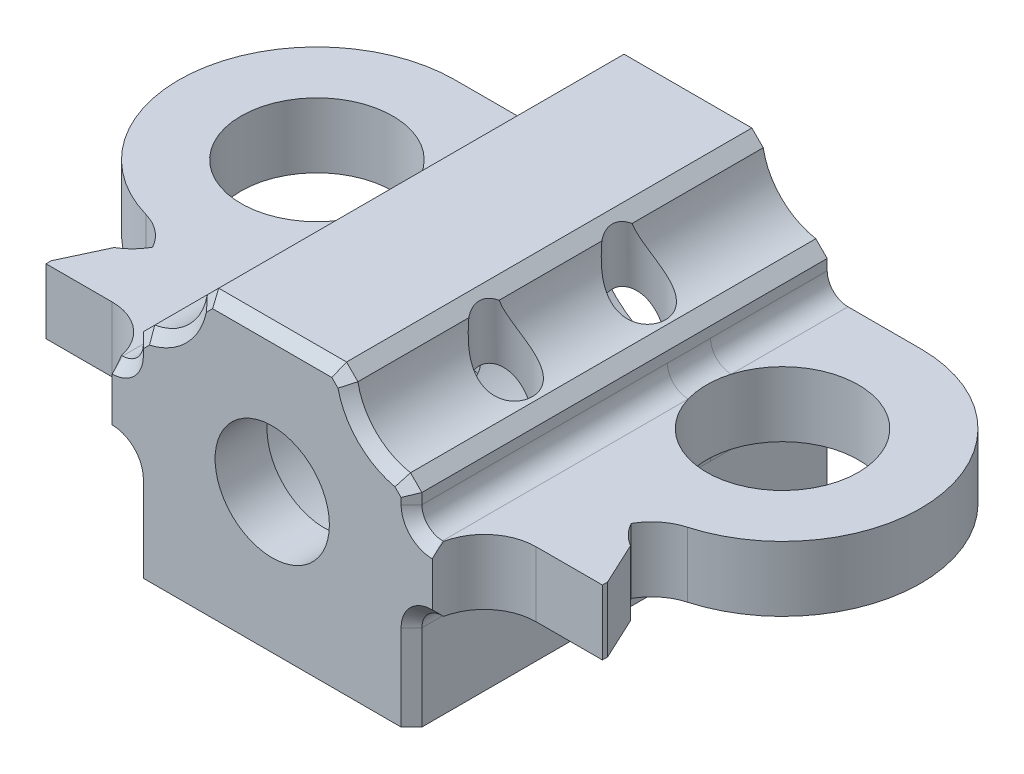
SolidWorks part; units mm, degrees
ref_plane "Front Plane" through (0, 0, 0) normal (0, 0, 1) x (1, 0, 0)
ref_plane "Top Plane" through (0, 0, 0) normal (0, 1, 0) x (1, 0, 0)
ref_plane "Right Plane" through (0, 0, 0) normal (1, 0, 0) x (0, 0, -1)
sketch "Sketch1" plane through (0, 0, 0) normal (0, 0, 1) x (1, 0, 0)
  line L0 (0, 0) -> (0, 69.4209) construction
  line L1 (8.509, 17.018) -> (-8.509, 17.018)
  line L2 (-8.509, 17.018) -> (-8.509, 0)
  line L3 (-8.509, 0) -> (8.509, 0)
  line L4 (8.509, 17.018) -> (8.509, 0)
  point P8 (0, 17.018)
  dimension "D1" = 17.018
  dimension "D2" = 17.018
extrude "Boss-Extrude1" add sketch "Sketch1" along normal blind 25.4
ref_plane "Plane1" through (0, 8.509, 0) normal (0, 1, 0) x (1, 0, 0)
sketch "Sketch2" plane through (0, 0, 0) normal (1, 0, 0) x (0, 0, -1)
  line L0 (-25.4, 8.509) -> (1.0345, 8.509) construction
  line L1 (-25.4, 0) -> (-25.4, 17.018) construction
  line L2 (-22.225, 14.859) -> (-15.3578, 14.859)
  line L3 (-22.225, 14.859) -> (-22.225, 12.0015)
  line L4 (-22.225, 12.0015) -> (-25.4, 12.0015)
  line L5 (-25.4, 12.0015) -> (-25.4, 8.509)
  line L6 (-15.3578, 14.859) -> (-15.3578, 3.977) construction
  line L7 (-25.4, 8.509) -> (-12.1828, 8.509)
  line L8 (-15.3578, 14.859) -> (0, 14.859)
  line L9 (0, 0) -> (0, 17.018) construction
  line L10 (-12.1828, 8.509) -> (0, 8.509)
  line L11 (0, 8.509) -> (0, 14.859)
  dimension "D1" = 12.7
  dimension "D2" = 6.985
  dimension "D3" = 3.175
revolve "Cut-Revolve1" cut sketch "Sketch2" angle 360 about L7
sketch "Sketch4" plane through (0, 0, 0) normal (0, -1, 0) x (1, 0, 0)
  line L1 (-6, 17.0663) -> (6, 17.0663) construction
  line L2 (-6, 17.0663) -> (-6, 9.0663) construction
  line L3 (-6, 9.0663) -> (6, 9.0663) construction
  line L4 (6, 17.0663) -> (6, 9.0663) construction
  line L5 (-6, 17.0663) -> (6, 9.0663) construction
  line L6 (-6, 9.0663) -> (6, 17.0663) construction
  line L15 (-8.509, 25.4) -> (8.509, 25.4) construction
  circle A0 centre (-6, 17.0663) radius 1.016
  circle A1 centre (5.938, 17.0663) radius 1.016
  circle A2 centre (5.938, 8.9383) radius 1.016
  circle A3 centre (-6, 8.9383) radius 1.016
  point P0 (0, 13.0663)
  dimension "D3" = 2.032
  dimension "D1" = 12
  dimension "D2" = 8
  dimension "D6" = 8.3337
  dimension "D4" = 2
  dimension "D5" = 2
extrude "Cut-Extrude2" cut sketch "Sketch4" against normal through all
sketch "Sketch5" plane through (0, 8.509, 0) normal (0, 1, 0) x (1, 0, 0)
  line L0 (8.509, 0) -> (14.224, 0)
  line L1 (16.9974, -21.9058) -> (15.776, -19.2866)
  line L2 (15.776, -19.2866) -> (14.224, -19.2866)
  line L3 (14.224, -19.2866) -> (14.224, -16.891)
  line L4 (8.509, -25.4) -> (16.9974, -25.4)
  line L5 (14.224, -8.4455) -> (21.1828, -23.3687) construction
  line L6 (16.9974, -21.9058) -> (16.9974, -25.4)
  line L7 (8.509, -25.4) -> (8.509, 0) construction
  line L8 (8.509, 0) -> (8.509, -25.4)
  line L10 (0, -25.4) -> (0, 11.748) construction
  line L11 (8.509, -25.4) -> (-8.509, -25.4) construction
  line L12 (14.224, -8.4455) -> (14.224, -36.5309) construction
  arc A0 (14.224, 0) -> (14.224, -16.891) centre (14.224, -8.4455) cw
  circle A1 centre (14.224, -8.4455) radius 4.6355
  dimension "D2" = 9.271
  dimension "D4" = 3.81
  dimension "D3" = 5.715
  dimension "D5" = 25
  dimension "D6" = 6.35
extrude "Boss-Extrude2" add sketch "Sketch5" against normal blind 1.9844 and the other way blind 1.9844
mirror "Mirror1" about plane through (0, 0, 0) normal (1, 0, 0) of "Boss-Extrude2"
fillet "Fillet2" radius 3.175 4 edges at (14.224, 8.509, 16.891) (14.224, 8.509, 19.2866) (-14.224, 8.509, 19.2866) (-14.224, 8.509, 16.891)
sketch "Sketch7" plane through (0, 0, 25.4) normal (0, 0, 1) x (1, 0, 0)
  line L0 (0, 19.0675) -> (0, -3.3693) construction
  circle A0 centre (8.509, 17.018) radius 3.9687
  circle A1 centre (-8.509, 17.018) radius 3.9687
  dimension "D1" = 7.9375
extrude "Cut-Extrude3" cut sketch "Sketch7" against normal through all
fillet "Fillet3" radius 1.27 4 edges
chamfer "Chamfer1" distance 0.635 angle 45 4 edges at (8.509, 13.0492, 12.7) (4.5402, 17.018, 12.7) (-4.5402, 17.018, 12.7) (-8.509, 13.0492, 12.7)
chamfer "Chamfer2" distance 0.635 angle 45 21 edges at (-8.881, 6.1527, 25.4) (-16.9974, 8.509, 25.4) (-8.881, 10.8653, 25.4) (-8.1607, 12.7626, 25.4) (-5.7027, 14.2117, 25.4) (-4.2536, 16.6697, 25.4) (8.881, 6.1527, 25.4) (16.9974, 8.509, 25.4) (8.881, 10.8653, 25.4) (8.1607, 12.7626, 25.4) (5.7027, 14.2117, 25.4) (4.2536, 16.6697, 25.4) (0, 17.018, 25.4)
sketch "Sketch8" plane through (0, 17.018, 0) normal (0, 1, 0) x (1, 0, 0)
  line L0 (-16.9974, -22.225) -> (-12.954, -22.225)
  line L1 (-16.9974, -24.765) -> (-16.9974, -21.9058) construction
  line L3 (-9.779, -25.4) -> (-16.3624, -25.4) construction
  line L4 (-16.9974, -22.225) -> (-16.9974, -25.4)
  line L5 (-16.9974, -25.4) -> (-9.779, -25.4)
  line L6 (0, -24.765) -> (0, -9.7356) construction
  line L7 (-3.9052, -24.765) -> (3.9052, -24.765) construction
  line L8 (16.9974, -25.4) -> (9.779, -25.4)
  line L9 (16.9974, -22.225) -> (16.9974, -25.4)
  line L10 (16.9974, -22.225) -> (12.954, -22.225)
  arc A0 (-12.954, -22.225) -> (-9.779, -25.4) centre (-12.954, -25.4) cw
  arc A1 (12.954, -22.225) -> (9.779, -25.4) centre (12.954, -25.4) ccw
  dimension "D1" = 3.175
extrude "Cut-Extrude4" cut sketch "Sketch8" against normal through all
sketch "Sketch9" plane through (0, 0, 0) normal (0, 0, -1) x (-1, 0, 0)
  line L0 (0, -2.2833) -> (0, 21.1526) construction
  line L1 (-6.35, 8.509) -> (9.7624, 8.509) construction
  line L2 (9.3599, 8.509) -> (-9.3599, 8.509) construction
  circle A0 centre (0, 8.509) radius 6.35 construction
  circle A1 centre (0, 8.509) radius 6.35 construction
  circle A2 centre (8.382, 8.509) radius 1.3335
  circle A3 centre (-8.382, 8.509) radius 1.3335
  dimension "D1" = 2.667
  dimension "D2" = 8.382
extrude "Cut-Extrude5" cut sketch "Sketch9" against normal blind 3.81
sketch "Sketch10" plane through (0, 17.018, 0) normal (0, 1, 0) x (1, 0, 0)
  line L0 (-0.031, -8.9383) -> (-0.031, -21.1529) construction
  line L1 (-6, -8.9383) -> (5.938, -8.9383) construction
  line L2 (-6, -8.9383) -> (-6, -17.0663) construction
  line L3 (-6, -17.0663) -> (5.938, -17.0663) construction
  line L4 (5.938, -8.9383) -> (5.938, -17.0663) construction
  line L5 (5.938, -13.0023) -> (-11.7995, -13.0023) construction
  circle A0 centre (5.938, -8.9383) radius 1.625
  circle A1 centre (-6, -8.9383) radius 1.625
  circle A2 centre (5.938, -17.0663) radius 1.625
  circle A3 centre (-6, -17.0663) radius 1.625
  dimension "D1" = 3.25
extrude "Cut-Extrude6" cut sketch "Sketch10" against normal blind 13.97
